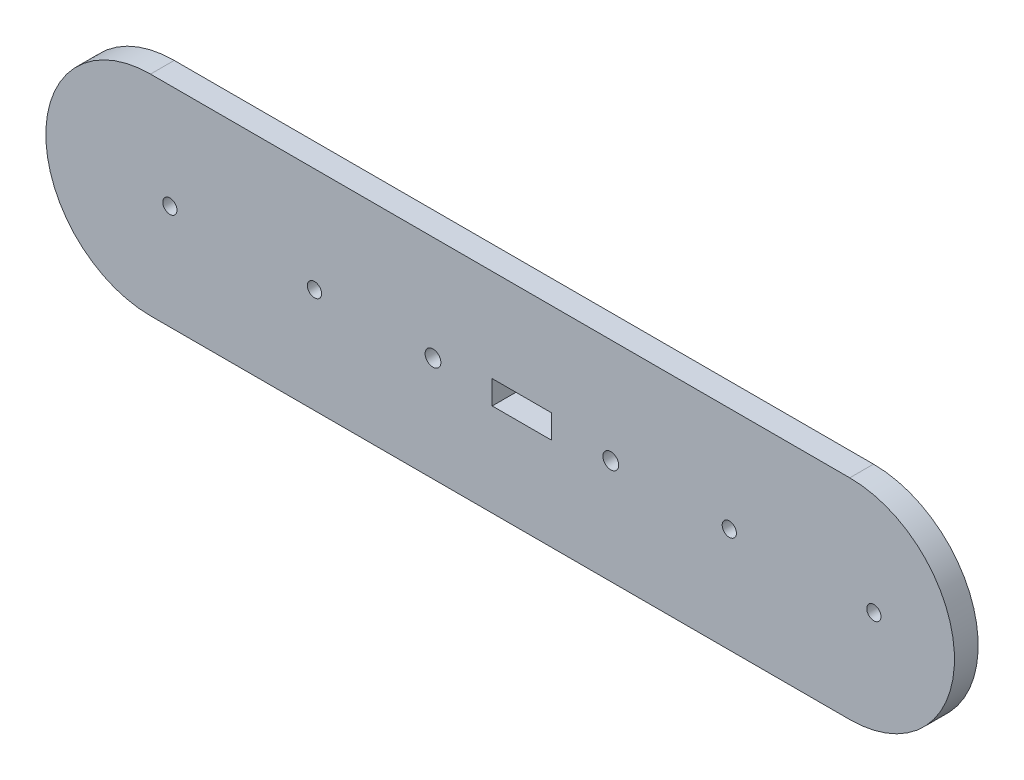
SolidWorks part; units mm, degrees
material "Balsa"
ref_plane "Plano frontal" through (0, 0, 0) normal (0, 0, 1) x (1, 0, 0)
ref_plane "Plano superior" through (0, 0, 0) normal (0, 1, 0) x (1, 0, 0)
ref_plane "Plano direito" through (0, 0, 0) normal (1, 0, 0) x (0, 0, -1)
sketch "Esboço1" plane through (0, 0, 0) normal (0, 0, 1) x (1, 0, 0)
  line L0 (-94, 26.5) -> (83, 26.5)
  line L1 (-94, -26.5) -> (83, -26.5)
  line L2 (-94, 0) -> (-20.5, 0) construction
  line L3 (-22.5, 0) -> (22.5, 0) construction
  line L4 (0, 11.6249) -> (0, -21.7831) construction
  line L5 (20.5, 0) -> (22.5, 0) construction
  line L7 (-7.5, -3) -> (7.5, -3)
  line L8 (-7.5, -3) -> (-7.5, 3)
  line L9 (-7.5, 3) -> (7.5, 3)
  line L10 (7.5, -3) -> (7.5, 3)
  line L11 (-7.5, -3) -> (7.5, 3) construction
  line L12 (-7.5, 3) -> (7.5, -3) construction
  arc A0 (83, -26.5) -> (83, 26.5) centre (83, 0) ccw
  arc A1 (-94, 26.5) -> (-94, -26.5) centre (-94, 0) ccw
  circle A4 centre (-22.5, 0) radius 2
  circle A5 centre (22.5, 0) radius 2
  circle A6 centre (-89.1, 0) radius 1.8
  circle A7 centre (-52.5, 0) radius 1.8
  circle A8 centre (52.5, 0) radius 1.8
  circle A9 centre (89.1, 0) radius 1.8
  point P8 (0, 0)
  point P19 (0, 0)
  dimension "D1" = 4
  dimension "D5" = 15
  dimension "D6" = 26.5
  dimension "D7" = 3.6
  dimension "D2" = 45
  dimension "D3" = 83
  dimension "D4" = 94
  dimension "D8" = 36.6
  dimension "D9" = 30
  dimension "D10" = 6
extrude "Ressalto-extrusão1" add sketch "Esboço1" along normal blind 6
